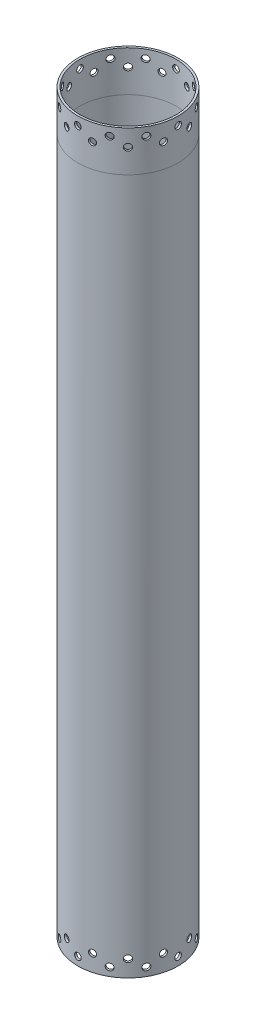
SolidWorks part; units mm, degrees
material "6061-T6 (SS)"
ref_plane "Front Plane" through (0, 0, 0) normal (0, 0, 1) x (1, 0, 0)
ref_plane "Top Plane" through (0, 0, 0) normal (0, 1, 0) x (1, 0, 0)
ref_plane "Right Plane" through (0, 0, 0) normal (1, 0, 0) x (0, 0, -1)
sketch "Sketch2" plane through (0, 0, 0) normal (0, 1, 0) x (1, 0, 0)
  circle A0 centre (0, 0) radius 76.2
  circle A1 centre (0, 0) radius 73.025
  dimension "D1" = 152.4
  dimension "D2" = 3.175
extrude "Boss-Extrude1" add sketch "Sketch2" along normal blind 1117.6
sketch "Sketch3" plane through (0, 0, 0) normal (0, 0, 1) x (1, 0, 0)
  line L0 (0, 1117.6) -> (0, 1104.9) construction
  line L1 (73.025, 1117.6) -> (-73.025, 1117.6) construction
  circle A0 centre (0, 1104.9) radius 5.0419
  dimension "D1" = 10.0838
  dimension "D2" = 12.7
extrude "Cut-Extrude1" cut sketch "Sketch3" against normal blind 1143
ref_plane "Plane1" through (-19.722, 0, 73.6035) normal (-0.2588, 0, 0.9659) x (0, -1, 0)
sketch "Sketch6" plane through (-19.722, 0, 73.6035) normal (-0.2588, 0, 0.9659) x (0, -1, 0)
  line L0 (-1117.6, 0) -> (-1092.2, 0) construction
  line L1 (-1117.6, 76.2) -> (-1117.6, -76.2) construction
  circle A0 centre (-1092.2, 0) radius 5.0419
  dimension "D1" = 10.0838
extrude "Cut-Extrude2" cut sketch "Sketch6" against normal blind 25.4
pattern_circular "CirPattern2" count 12 over 360 about axis through (0, 1117.6, 0) along (0, -1, 0) of "Cut-Extrude2", "Cut-Extrude1"
ref_plane "Plane2" through (0, 558.8, 0) normal (0, 1, 0) x (1, 0, 0)
mirror "Mirror1" about plane through (0, 558.8, 0) normal (0, 1, 0) of "CirPattern2"
ref_axis "Axis1" through (-69.9555, 1104.9, -40.3888) along (0.866, 0, 0.5)
ref_axis "Axis2" through (-40.3884, 1104.9, -69.9547) along (0.5, 0, 0.866)
ref_plane "Plane3" through (0, 1104.9, 0) normal (0, -1, 0) x (-1, 0, 0)
ref_axis "Axis3" through (-67.6049, 1092.2, -18.1147) along (-0.9659, 0, -0.2588)
ref_axis "Axis4" through (-47.674, 1092.2, -47.674) along (-0.7071, 0, -0.7071)
ref_plane "Plane4" through (0, 1092.2, 0) normal (0, 1, 0) x (1, 0, 0)
ref_plane "Plane5" through (0, 0, 0) normal (-0.5, 0.0045, 0.866) x (0.866, 0.0026, 0.5)
split line "Split Line2"
split line "Split Line3"
ref_axis "Axis5" through (47.674, 25.4, 47.674) along (0.7071, 0, 0.7071)
ref_axis "Axis6" through (67.6049, 25.4, 18.1147) along (0.9659, 0, 0.2588)
ref_axis "Axis7" through (69.9555, 12.7, 40.3888) along (-0.866, 0, -0.5)
ref_axis "Axis8" through (76.2, 12.7, 0) along (-1, 0, 0)
ref_plane "Plane7" through (0, 25.4, 0) normal (0, 1, 0) x (1, 0, 0)
ref_plane "Plane8" through (0, 12.7, 0) normal (0, 1, 0) x (1, 0, 0)
split line "Split Line4"
split line "Split Line5"
ref_plane "Plane9" through (0, 1055.878, 0) normal (0, 1, 0) x (1, 0, 0)
split line "Split Line6"
ref_plane "Plane10" through (0, 61.722, 0) normal (0, -1, 0) x (-1, 0, 0)
split line "Split Line11"
split line "Split Line12"
equation "\"holeDia\"=0.397"
equation "\"D1@Sketch3\"=\"holeDia\""
equation "\"D1@Sketch6\"=\"holeDia\""
equation "\"numHoles\"=12"
equation "\"D1@CirPattern2\"=\"numHoles\""
equation "\"D1@Plane1\"=180/\"numHoles\""
